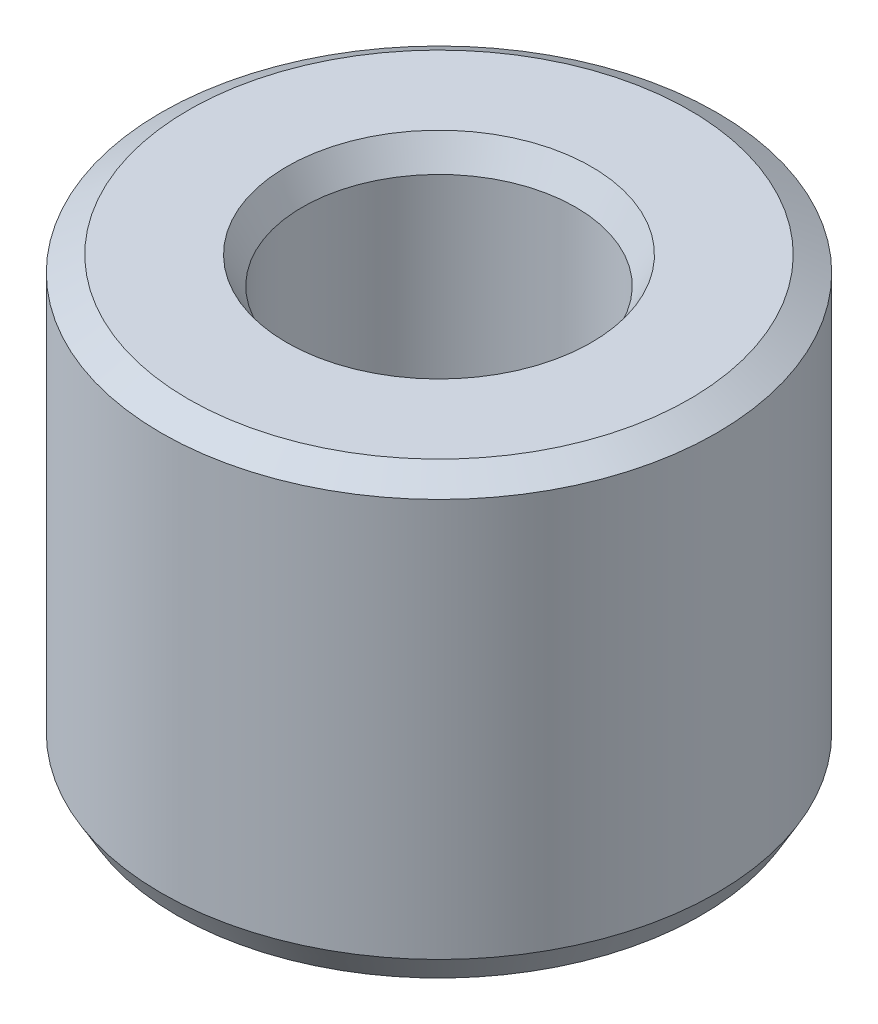
SolidWorks part; units mm, degrees
ref_plane "Front Plane" through (0, 0, 0) normal (0, 0, 1) x (1, 0, 0)
ref_plane "Top Plane" through (0, 0, 0) normal (0, 1, 0) x (1, 0, 0)
ref_plane "Right Plane" through (0, 0, 0) normal (1, 0, 0) x (0, 0, -1)
sketch "Sketch1" plane through (0, 0, 0) normal (0, 1, 0) x (1, 0, 0)
  circle A0 centre (0, 0) radius 35
  dimension "SLEEVE_OD" = 70
extrude "Boss-Extrude1" add sketch "Sketch1" along normal blind 55.6202
sketch "Sketch2" plane through (0, 0, 0) normal (0, 1, 0) x (1, 0, 0)
  circle A0 centre (0, 0) radius 17.2253
  dimension "BORE_D" = 34.4506
extrude "Cut-Extrude1" cut sketch "Sketch2" along normal through all
chamfer "Chamfer1" distance 1.9794 angle 60 4 edges at (0, 55.6202, 17.2253) (0, 0, 17.2253) (0, 0, 35) (0, 55.6202, 35) first distance on face at (0, 55.6202, 17.2253) first distance on face at (0, 0, 17.2253) first distance on face at (0, 55.6202, 35)
